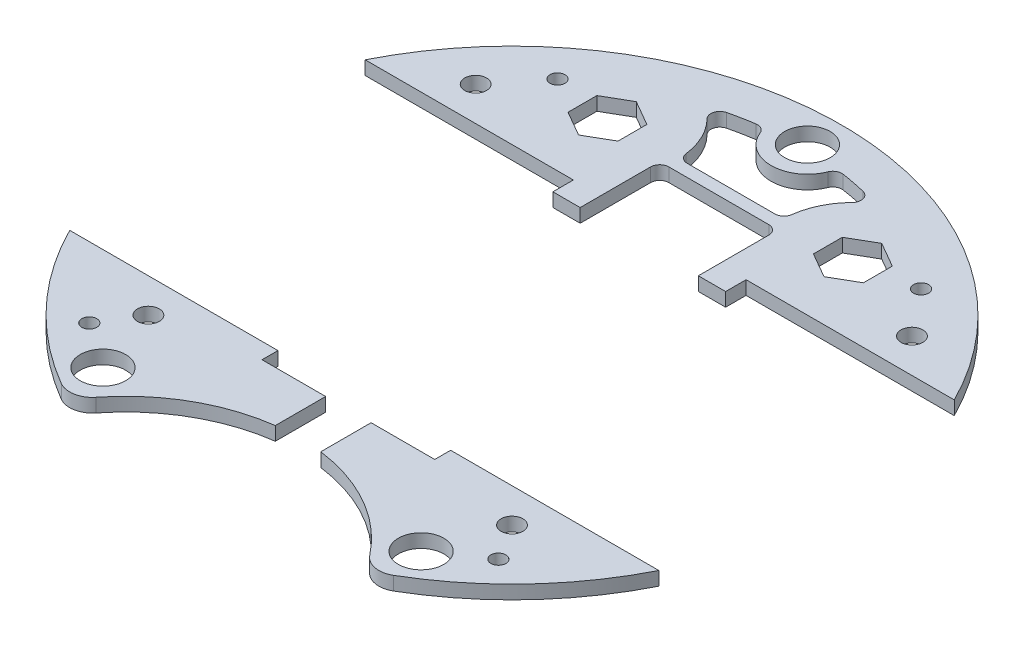
SolidWorks part; units mm, degrees
material "Acrylic (Medium-high impact)"
ref_plane "Front Plane" through (0, 0, 0) normal (0, 0, 1) x (1, 0, 0)
ref_plane "Top Plane" through (0, 0, 0) normal (0, 1, 0) x (1, 0, 0)
ref_plane "Right Plane" through (0, 0, 0) normal (1, 0, 0) x (0, 0, -1)
sketch "Sketch1" plane through (0, 0, 0) normal (0, 1, 0) x (1, 0, 0)
  line L0 (0, -85) -> (-32.4891, -64.8129) construction
  line L1 (0, -85) -> (0, 0) construction
  arc A0 (36.5434, -62.6165) -> (-36.5434, -62.6165) centre (0, 0) ccw
  arc A1 (30.0898, -61.3851) -> (-30.0898, -61.3851) centre (0, -85) ccw
  arc A2 (36.5434, -62.6165) -> (30.0898, -61.3851) centre (34.0231, -58.2982) cw
  arc A3 (-30.0898, -61.3851) -> (-36.5434, -62.6165) centre (-34.0231, -58.2982) cw
  dimension "D1" = 145
  dimension "D2" = 76.5
  dimension "D4" = 5
  dimension "D3" = 85
extrude "Boss-Extrude1" add sketch "Sketch1" along normal blind 3
sketch "solenoid placement" plane through (0, 3, 0) normal (0, 1, 0) x (1, 0, 0)
  line L4 (-19, -36) -> (19, -36)
  line L5 (-19, 28) -> (-19, -36)
  line L6 (19, 28) -> (-19, 28)
  line L7 (19, -36) -> (19, 28)
  line L8 (-19, -36) -> (19, -36)
  line L9 (-19, 28) -> (-19, -36)
  line L10 (19, 28) -> (-19, 28)
  line L11 (19, -36) -> (19, 28)
  dimension "D1" = 0
extrude "Cut-Extrude1" cut sketch "solenoid placement" against normal through all
sketch "Sketch4" plane through (0, 3, 0) normal (0, 1, 0) x (1, 0, 0)
  line L6 (19, 28) -> (-19, 28) construction
  line L10 (-13, 28) -> (13, 28)
  line L11 (13, 28) -> (13, 43.5)
  line L12 (11, 45.5) -> (-11, 45.5)
  line L13 (-13, 43.5) -> (-13, 28)
  arc A5 (13, 43.5) -> (11, 45.5) centre (11, 43.5) ccw
  arc A7 (-11, 45.5) -> (-13, 43.5) centre (-11, 43.5) ccw
  point P10 (0, 28)
  point P11 (0, 28)
  dimension "D3" = 2
  dimension "D1" = 26
  dimension "D2" = 17.5
extrude "Cut-Extrude4" cut sketch "Sketch4" against normal through all
sketch "Sketch5" plane through (0, 3, 0) normal (0, 1, 0) x (1, 0, 0)
  line L6 (0, 0) -> (0, 72.5) construction
  line L7 (-21.5, 51.1754) -> (-27, 54.3509)
  line L8 (-27, 54.3509) -> (-32.5, 51.1754)
  line L9 (-32.5, 51.1754) -> (-32.5, 44.8246)
  line L10 (-32.5, 44.8246) -> (-27, 41.6491)
  line L11 (-27, 41.6491) -> (-21.5, 44.8246)
  line L12 (-21.5, 44.8246) -> (-21.5, 51.1754)
  line L13 (21.5, 44.8246) -> (21.5, 51.1754)
  line L14 (27, 41.6491) -> (21.5, 44.8246)
  line L15 (32.5, 44.8246) -> (27, 41.6491)
  line L16 (32.5, 51.1754) -> (32.5, 44.8246)
  line L17 (27, 54.3509) -> (32.5, 51.1754)
  line L18 (21.5, 51.1754) -> (27, 54.3509)
  circle A0 centre (-27, 48) radius 5.5 construction
  arc A1 (36.5434, -62.6165) -> (-36.5434, -62.6165) centre (0, 0) ccw construction
  circle A2 centre (27, 48) radius 5.5 construction
  dimension "D1" = 11
extrude "Cut-Extrude5" cut sketch "Sketch5" against normal through all
sketch "Sketch6" plane through (0, 3, 0) normal (0, 1, 0) x (1, 0, 0)
  circle A1 centre (40, -40) radius 2.4
  circle A2 centre (40, -40) radius 2.4
  circle A3 centre (-40, -40) radius 2.4
  circle A4 centre (-40, -40) radius 2.4
  circle A5 centre (48, 40) radius 2.4
  circle A6 centre (48, 40) radius 2.4
  circle A7 centre (-48, 40) radius 2.4
  circle A8 centre (-48, 40) radius 2.4
  dimension "D1" = 0
  dimension "D2" = 0
  dimension "D3" = 0
  dimension "D4" = 0
extrude "Cut-Extrude6" cut sketch "Sketch6" against normal through all
sketch "Sketch3" plane through (0, 3, 0) normal (0, 1, 0) x (1, 0, 0)
  line L0 (-19, 28) -> (-19, 32.5)
  line L1 (72.5, -32.5) -> (-72.5, -32.5)
  line L2 (72.5, -32.5) -> (72.5, 32.5)
  line L3 (72.5, 32.5) -> (19, 32.5)
  line L4 (-72.5, -32.5) -> (-72.5, 32.5)
  line L5 (72.5, -32.5) -> (-72.5, 32.5) construction
  line L6 (72.5, 32.5) -> (-72.5, -32.5) construction
  line L7 (-19, 28) -> (19, 28)
  line L8 (19, 28) -> (19, 32.5)
  line L9 (-19, 32.5) -> (-72.5, 32.5)
  arc A0 (36.5434, -62.6165) -> (-36.5434, -62.6165) centre (0, 0) ccw construction
  point P0 (0, 0)
  dimension "D1" = 65
extrude "Cut-Extrude3" cut sketch "Sketch3" against normal through all
sketch "Sketch7" plane through (0, 3, 0) normal (0, 1, 0) x (1, 0, 0)
  line L5 (-5, 0) -> (5, 0)
  line L6 (-5, 0) -> (-5, -50)
  line L7 (-5, -50) -> (5, -50)
  line L8 (5, 0) -> (5, -50)
  point P4 (0, 0)
  dimension "D1" = 10
  dimension "D2" = 50
extrude "Cut-Extrude7" cut sketch "Sketch7" against normal through all
sketch "Sketch9" plane through (0, 3, 0) normal (0, -1, 0) x (1, 0, 0)
  circle A1 centre (35, 55) radius 5
  circle A2 centre (35, 55) radius 5
  circle A3 centre (-35, 55) radius 5
  circle A4 centre (-35, 55) radius 5
  dimension "D1" = 0
  dimension "D2" = 0
extrude "Cut-Extrude11" cut sketch "Sketch9" along normal through all
sketch "Sketch10" plane through (0, 3, 0) normal (0, 1, 0) x (1, 0, 0)
  circle A1 centre (0, 65) radius 5
  circle A2 centre (0, 65) radius 5
  dimension "D1" = 0
extrude "Cut-Extrude12" cut sketch "Sketch10" against normal through all and the other way through all
sketch "Sketch11" plane through (0, 3, 0) normal (0, 1, 0) x (1, 0, 0)
  line L0 (0, 0) -> (0, -22.1714) construction
  circle A0 centre (45, -48) radius 1.65
  circle A1 centre (-45, -48) radius 1.65
  circle A2 centre (40, 50) radius 1.65
  circle A4 centre (-40, 50) radius 1.65
  point P9 (0, 0)
  point P11 (67.1523, 71.4895)
  point P15 (-1.2909, 2.0156)
  dimension "D3" = 3.3
  dimension "D1" = 45
  dimension "D2" = 48
  dimension "D4" = 40
  dimension "D5" = 50
extrude "Cut-Extrude13" cut sketch "Sketch11" against normal through all
sketch "Sketch13" plane through (0, 3, 0) normal (0, 1, 0) x (1, 0, 0)
  line L10 (-11.5013, 48.2) -> (11.5013, 48.2)
  line L11 (-9.6388, 48.2) -> (9.6388, 48.2)
  arc A8 (14.9949, 62.2186) -> (15.9519, 58.8715) centre (14.5263, 60.2743) cw
  arc A9 (7.4323, 62.04) -> (9.59, 63.2774) centre (9.2903, 61.3) cw
  arc A10 (9.6388, 48.2) -> (11.623, 49.9486) centre (9.6388, 50.2) ccw
  arc A11 (-9.6388, 48.2) -> (-11.623, 49.9486) centre (-9.6388, 50.2) cw
  arc A28 (-9.59, 63.2774) -> (-7.4323, 62.04) centre (-9.2903, 61.3) cw
  arc A29 (-11.5013, 48.2) -> (-18.8249, 61.1688) centre (-27, 48) ccw
  arc A30 (-7.861, 63.5154) -> (-18.8249, 61.1688) centre (0, 0) ccw
  arc A31 (-7.861, 63.5154) -> (7.861, 63.5154) centre (0, 65) ccw
  arc A32 (18.8249, 61.1688) -> (7.861, 63.5154) centre (0, 0) ccw
  arc A33 (18.8249, 61.1688) -> (11.5013, 48.2) centre (27, 48) ccw
  arc A34 (-11.623, 49.9486) -> (-15.9519, 58.8715) centre (-27, 48) ccw
  arc A35 (-9.59, 63.2774) -> (-14.9949, 62.2186) centre (0, 0) ccw
  arc A36 (-7.4323, 62.04) -> (7.4323, 62.04) centre (0, 65) ccw
  arc A37 (14.9949, 62.2186) -> (9.59, 63.2774) centre (0, 0) ccw
  arc A38 (15.9519, 58.8715) -> (11.623, 49.9486) centre (27, 48) ccw
  arc A39 (-15.9519, 58.8715) -> (-14.9949, 62.2186) centre (-14.5263, 60.2743) cw
  point P0 (0, 0)
  dimension "D2" = 2
  dimension "D1" = 0
extrude "Cut-Extrude14" cut sketch "Sketch13" against normal through all contours A38 A37 A36 A35 A34 L11 region at (0, 3, -55.216)
equation "\"smallPulleyTeeth\"= 30"
equation "\"largePulleyTeeth\"= 30"
equation "\"eighthThick\"= 3.0mm"
equation "\"sixteenthThick\" = 1.7mm"
equation "\"quarterThick\"=6.0mm"
equation "\"OD\" = 145mm"
equation "\"puckAngle\" = 60.5deg"
equation "\"D1@Sketch1\"=\"OD\""
equation "\"puckDiam\" = 76.5mm"
equation "\"D2@Sketch1\"=\"puckDiam\""
equation "\"D1@Boss-Extrude1\"=\"eighthThick\""
equation "\"axlePress\" = 5.9mm"
equation "\"press\" = 0.2mm"
equation "\"wheelClear\" = 0.3mm"
equation "\"10-32clear\" = 4.8mm"
equation "\"6-32clear\" = 3.3mm"
equation "\"8-32clear\" = 4.0mm"
equation "\"wheelHeight\" = 22mm"
equation "\"wheelWell\" = 65mm"
equation "\"D1@Sketch3\"=\"wheelWell\""
equation "\"puckDist\" = 85mm"
equation "\"scoopFillet\" = 5mm"
equation "\"4-40clear\" = 3.0mm"
equation "\"D3@Sketch1\"=\"puckDist\""
equation "\"D4@Sketch1\"=\"scoopFillet\""
equation "\"D3@Sketch11\"=\"6-32clear\""
